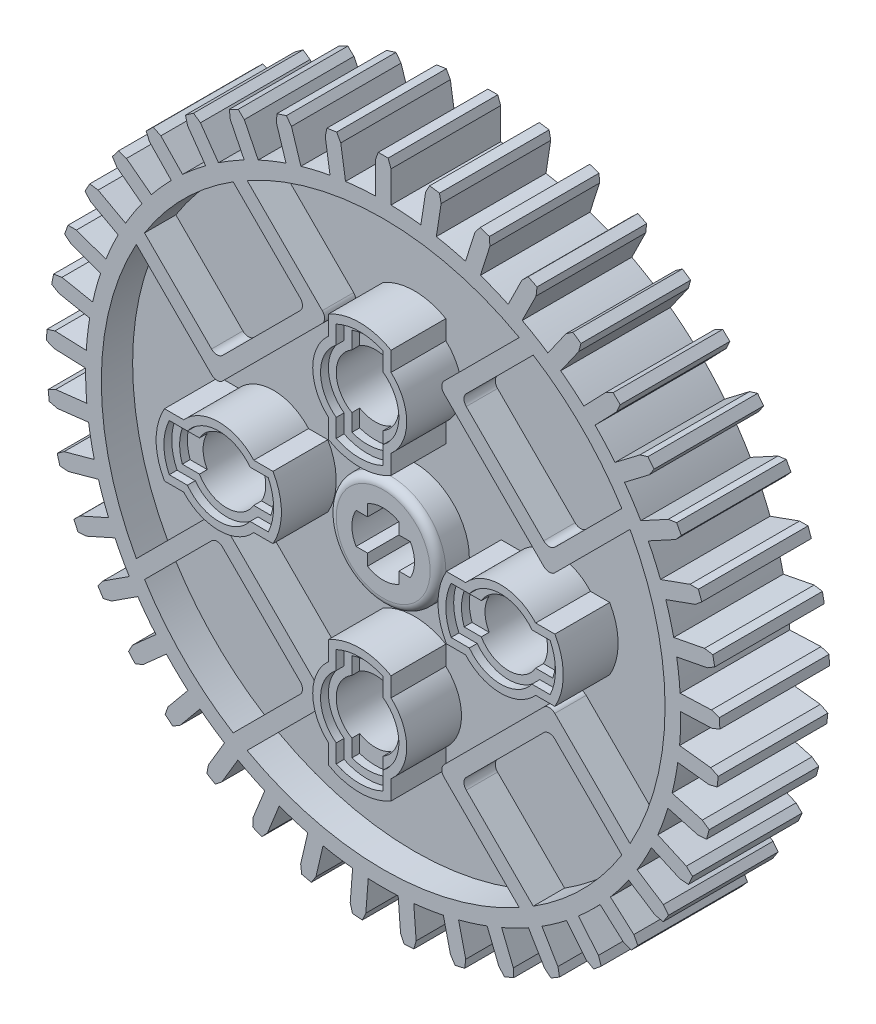
SolidWorks part; units mm, degrees
material "PBT General Purpose"
ref_plane "Front Plane" through (0, 0, 0) normal (0, 0, 1) x (1, 0, 0)
ref_plane "Top Plane" through (0, 0, 0) normal (0, 1, 0) x (1, 0, 0)
ref_plane "Right Plane" through (0, 0, 0) normal (1, 0, 0) x (0, 0, -1)
sketch "Sketch1" plane through (0, 0, 0) normal (0, 0, 1) x (1, 0, 0)
  line L1 (-1, -1.7321) -> (1, -1.7321)
  line L2 (-1, -1.7321) -> (-1, 1.7321)
  line L3 (-1, 1.7321) -> (1, 1.7321)
  line L4 (1, -1.7321) -> (1, 1.7321)
  line L5 (-1, -1.7321) -> (1, 1.7321) construction
  line L6 (-1, 1.7321) -> (1, -1.7321) construction
  line L7 (-1.7321, -1) -> (1.7321, -1)
  line L8 (-1.7321, -1) -> (-1.7321, 1)
  line L9 (-1.7321, 1) -> (1.7321, 1)
  line L10 (1.7321, -1) -> (1.7321, 1)
  line L11 (-1.7321, -1) -> (1.7321, 1) construction
  line L12 (-1.7321, 1) -> (1.7321, -1) construction
  circle A0 centre (0, 0) radius 19
  circle A1 centre (0, 0) radius 2
  dimension "D1" = 38
  dimension "D2" = 4
  dimension "D3" = 2
extrude "Boss-Extrude1" add sketch "Sketch1" along normal mid plane 7 contours A0 A1 | L4 A1 L7 | L7 A1 L2 | L2 A1 L9 | L9 A1 L4 region at (-1.2652, -1.2652, 0) region at (1.2652, -1.2652, 0) region at (-1.2652, 1.2652, 0) region at (1.2652, 1.2652, 0) region at (-18.4626, 0, 0)
sketch "Sketch3" plane through (0, 0, 3.5) normal (0, 0, 1) x (1, 0, 0)
  circle A0 centre (0, 0) radius 3.5
  circle A1 centre (0, 0) radius 18
  dimension "D1" = 36
  dimension "D2" = 7
extrude "Cut-Extrude1" cut sketch "Sketch3" against normal blind 2
mirror "Mirror2" about plane through (0, 0, 0) normal (0, 0, 1) of "Cut-Extrude1"
sketch "Sketch4" plane through (0, 0, 1.5) normal (0, 0, 1) x (1, 0, 0)
  line L0 (-16.5613, -16.5613) -> (17.9113, 17.9113) construction
  line L1 (9.5812, 15.2381) -> (4.9497, 10.6066)
  line L2 (4.9497, 10.6066) -> (10.6066, 4.9497)
  line L3 (10.6066, 4.9497) -> (15.2381, 9.5812)
  line L4 (8.6915, 15.7626) -> (3.5355, 10.6066)
  line L5 (3.5355, 10.6066) -> (10.6066, 3.5355)
  line L6 (10.6066, 3.5355) -> (15.7626, 8.6915)
  line L7 (10.6066, 3.5355) -> (16.497, 9.4259) construction
  line L8 (9.4259, 16.497) -> (3.5355, 10.6066) construction
  circle A0 centre (0, 0) radius 18 construction
  arc A3 (15.7626, 8.6915) -> (15.2381, 9.5812) centre (0, 0) ccw
  arc A4 (16.497, 9.4259) -> (9.4259, 16.497) centre (0, 0) ccw construction
  arc A5 (9.5812, 15.2381) -> (8.6915, 15.7626) centre (0, 0) ccw
  arc A6 (15.2381, 9.5812) -> (9.5812, 15.2381) centre (0, 0) ccw construction
  point P6 (7.7782, 7.7782)
  dimension "D1" = 8
  dimension "D2" = 11
  dimension "D3" = 1
extrude "Boss-Extrude2" add sketch "Sketch4" along normal up to surface (2 mm away) and the other way up to surface (5 mm away) up to face at (18, 0, 3.5) other way up to face at (0, 0, -3.5)
fillet "Fillet2" radius 0.5 8 edges at (10.6066, 3.5355, 2.5) (3.5355, 10.6066, 2.5) (4.9497, 10.6066, 2.5) (10.6066, 4.9497, 2.5) (4.9497, 10.6066, -2.5) (10.6066, 4.9497, -2.5) (3.5355, 10.6066, -2.5) (10.6066, 3.5355, -2.5)
pattern_circular "CirPattern5" count 4 over 360 about axis through (0, 0, -3.5) along (0, 0, 1) of "Fillet2", "Boss-Extrude2"
sketch "Sketch5" plane through (0, 0, 1.5) normal (0, 0, 1) x (1, 0, 0)
  line L0 (0, -19.7835) -> (0, 18) construction
  line L2 (-1.5, 5.8377) -> (1.5, 5.8377)
  line L3 (-1.5, 5.8377) -> (-1.5, 12.1623)
  line L4 (-1.5, 12.1623) -> (1.5, 12.1623)
  line L5 (1.5, 5.8377) -> (1.5, 12.1623)
  line L6 (-1.5, 5.8377) -> (1.5, 12.1623) construction
  line L7 (-1.5, 12.1623) -> (1.5, 5.8377) construction
  arc A1 (8.6915, 15.7626) -> (-8.6915, 15.7626) centre (0, 0) ccw construction
  circle A3 centre (0, 9) radius 2.5
  circle A4 centre (0, 9) radius 3.5
  dimension "D1" = 5
  dimension "D2" = 7
  dimension "D4" = 9
  dimension "D3" = 3
extrude "Boss-Extrude3" add sketch "Sketch5" along normal blind 3 contours L3 A3 | L5 A3 | A3 L3 L2 L5 | L2 A4 | A3 L5 L4 L3 | L4 A4 | L5 A3 L3 region at (0, 6.2616, 1.5) region at (0, 5.7021, 1.5) region at (-1.9078, 9, 1.5) region at (0, 9, 1.5) region at (0, 11.7384, 1.5) region at (0, 12.2979, 1.5) region at (1.9078, 9, 1.5)
sketch "Sketch7" plane through (0, 0, 4.5) normal (0, 0, 1) x (1, 0, 0)
  line L8 (-1, 7.2679) -> (-1, 6.1716)
  line L9 (1, 6.1716) -> (1, 7.2679)
  line L10 (1, 10.7321) -> (1, 11.8284)
  line L11 (-1, 11.8284) -> (-1, 10.7321)
  line L12 (-1, 7.2679) -> (-1, 6.1716)
  line L13 (1, 6.1716) -> (1, 7.2679)
  line L14 (1, 10.7321) -> (1, 11.8284)
  line L15 (-1, 11.8284) -> (-1, 10.7321)
  arc A8 (-1, 10.7321) -> (-1, 7.2679) centre (0, 9) ccw
  arc A9 (-1, 6.1716) -> (1, 6.1716) centre (0, 9) ccw
  arc A10 (1, 7.2679) -> (1, 10.7321) centre (0, 9) ccw
  arc A11 (1, 11.8284) -> (-1, 11.8284) centre (0, 9) ccw
  arc A12 (-1, 10.7321) -> (-1, 7.2679) centre (0, 9) ccw
  arc A13 (-1, 6.1716) -> (1, 6.1716) centre (0, 9) ccw
  arc A14 (1, 7.2679) -> (1, 10.7321) centre (0, 9) ccw
  arc A15 (1, 11.8284) -> (-1, 11.8284) centre (0, 9) ccw
  dimension "D1" = 0.5
extrude "Cut-Extrude3" cut sketch "Sketch7" against normal blind 0.5
sketch "Sketch8" plane through (0, 0, 4) normal (0, 0, 1) x (1, 0, 0)
  circle A0 centre (0, 9) radius 2
  dimension "D1" = 4
extrude "Cut-Extrude4" cut sketch "Sketch8" against normal through all both and the other way through all
sketch "Sketch9" plane through (0, 0, 4.5) normal (0, 0, 1) x (1, 0, 0)
  line L4 (-1.5, 7) -> (-1.5, 5.8377)
  line L5 (1.5, 5.8377) -> (1.5, 7)
  line L6 (1.5, 11) -> (1.5, 12.1623)
  line L7 (-1.5, 12.1623) -> (-1.5, 11)
  line L8 (-2, 6.7639) -> (-2, 5.5359)
  line L9 (2, 5.5359) -> (2, 6.7639)
  line L10 (2, 11.2361) -> (2, 12.4641)
  line L11 (-2, 12.4641) -> (-2, 11.2361)
  line L12 (-2, 6.7639) -> (-2, 5.5359)
  line L13 (2, 5.5359) -> (2, 6.7639)
  line L14 (2, 11.2361) -> (2, 12.4641)
  line L15 (-2, 12.4641) -> (-2, 11.2361)
  arc A4 (-1.5, 11) -> (-1.5, 7) centre (0, 9) ccw
  arc A5 (-1.5, 5.8377) -> (1.5, 5.8377) centre (0, 9) ccw
  arc A6 (1.5, 7) -> (1.5, 11) centre (0, 9) ccw
  arc A7 (1.5, 12.1623) -> (-1.5, 12.1623) centre (0, 9) ccw
  arc A8 (-2, 11.2361) -> (-2, 6.7639) centre (0, 9) ccw
  arc A9 (-2, 5.5359) -> (2, 5.5359) centre (0, 9) ccw
  arc A10 (2, 6.7639) -> (2, 11.2361) centre (0, 9) ccw
  arc A11 (2, 12.4641) -> (-2, 12.4641) centre (0, 9) ccw
  arc A12 (-2, 11.2361) -> (-2, 6.7639) centre (0, 9) ccw
  arc A13 (-2, 5.5359) -> (2, 5.5359) centre (0, 9) ccw
  arc A14 (2, 6.7639) -> (2, 11.2361) centre (0, 9) ccw
  arc A15 (2, 12.4641) -> (-2, 12.4641) centre (0, 9) ccw
  dimension "D1" = 0.5
  dimension "D2" = 0.5
extrude "Boss-Extrude5" add sketch "Sketch9" against normal up to surface (3 mm away) and the other way blind 0.5 up to face at (3.5, 0, 1.5)
pattern_circular "CirPattern2" count 4 over 360 about axis through (0, 0, 3.5) along (0, 0, 1) of "Boss-Extrude3", "Cut-Extrude3", "Boss-Extrude5", "Cut-Extrude4"
mirror "Mirror6" about plane through (0, 0, 0) normal (0, 0, 1) of "CirPattern2"
sketch "Sketch10" plane through (0, 0, 0) normal (0, 0, 1) x (1, 0, 0)
  line L0 (0, 0) -> (0, 21.5) construction
  line L1 (-0.5, 18.9934) -> (-0.5, 20.9934)
  line L5 (0.5, 20.9934) -> (0.5, 18.9934)
  line L6 (-0.5, 20.9934) -> (-0.3156, 21.5)
  line L7 (-0.3156, 21.5) -> (0.3156, 21.5)
  line L8 (0.3156, 21.5) -> (0.5, 20.9934)
  circle A0 centre (0, 0) radius 19 construction
  arc A1 (0.5, 18.9934) -> (-0.5, 18.9934) centre (0, 0) ccw
  point P7 (0, 21.5)
  dimension "D1" = 21.5
  dimension "D2" = 1
  dimension "D3" = 20
  dimension "D4" = 2
extrude "Boss-Extrude6" add sketch "Sketch10" along normal up to surface and the other way up to surface up to face at (0, 0, 3.5) other way up to face at (0, 0, -3.5)
pattern_circular "CirPattern7" count 41 over 360 about axis through (0, 0, 3.5) along (0, 0, 1) of "Boss-Extrude6"
fillet "Fillet3" radius 0.5 2 edges at (3.5, 0, -3.5) (3.5, 0, 3.5)
